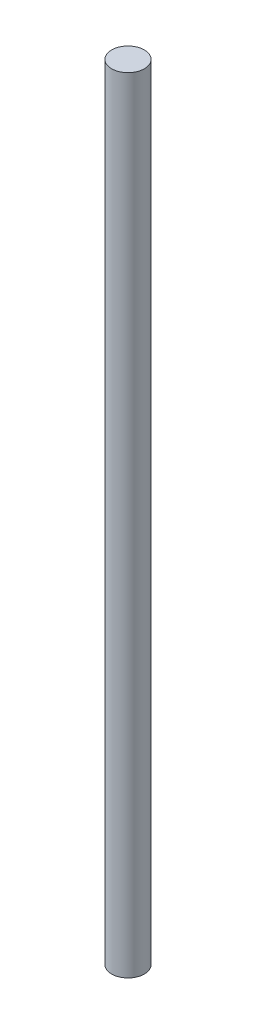
SolidWorks part; units mm, degrees
ref_plane "Front Plane" through (0, 0, 0) normal (0, 0, 1) x (1, 0, 0)
ref_plane "Top Plane" through (0, 0, 0) normal (0, 1, 0) x (1, 0, 0)
ref_plane "Right Plane" through (0, 0, 0) normal (1, 0, 0) x (0, 0, -1)
sketch "Sketch1" plane through (0, 0, 0) normal (0, 1, 0) x (1, 0, 0)
  circle A0 centre (0, 0) radius 6.35
  dimension "D1" = 12.7
extrude "Boss-Extrude1" add sketch "Sketch1" along normal mid plane 304.8
